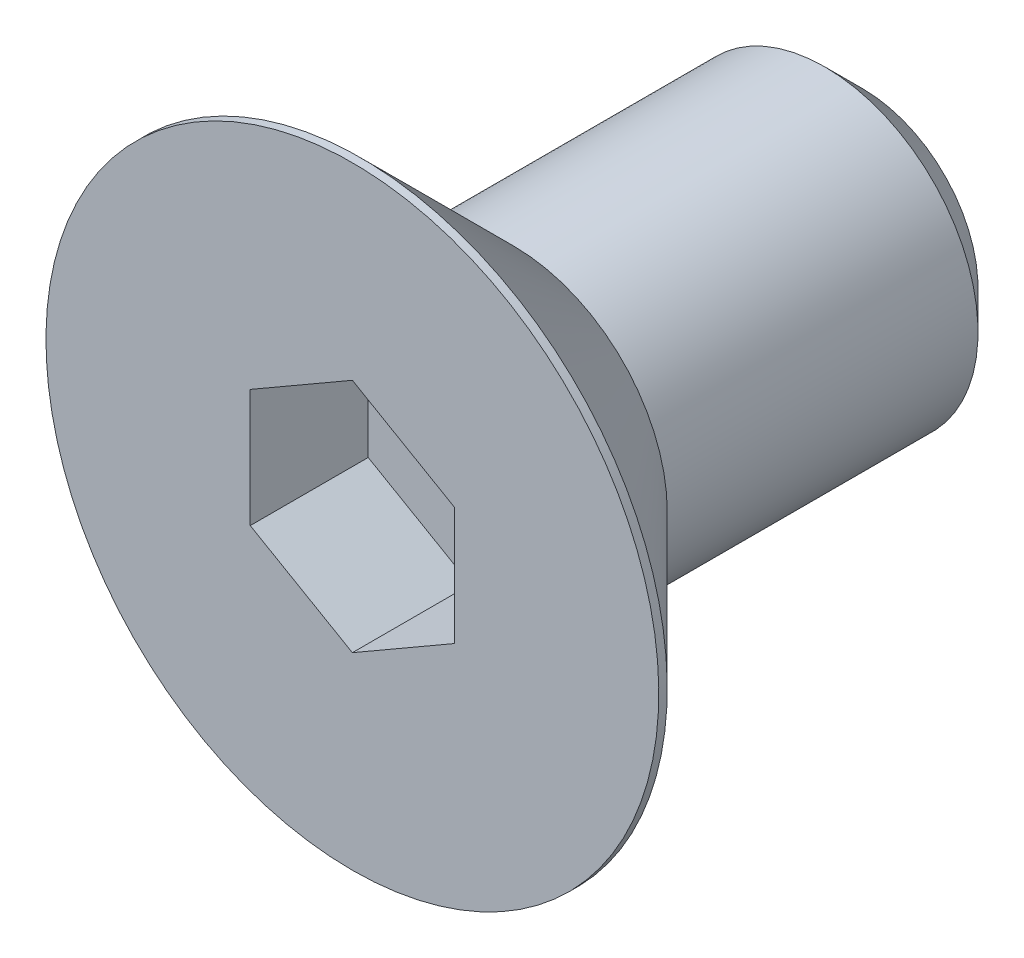
SolidWorks part; units mm, degrees
material "Chrome Stainless Steel"
ref_plane "Front" through (0, 0, 0) normal (0, 0, 1) x (1, 0, 0)
ref_plane "Top" through (0, 0, 0) normal (0, 1, 0) x (1, 0, 0)
ref_plane "Right" through (0, 0, 0) normal (1, 0, 0) x (0, 0, -1)
sketch "Sketch11" plane through (0, 0, 0) normal (1, 0, 0) x (0, 0, -1)
  line L0 (-5, 6) -> (5, 6) construction
  line L5 (-5, 6) -> (-5, -6) construction
  line L6 (5, 3) -> (5, -3) construction
  line L7 (-4.99, 2) -> (-4.99, -2) construction
  line L8 (4.9375, 3.1083) -> (5.9375, 3.1083) construction
  line L9 (5.9375, 3.1083) -> (5.4375, 2.2422) construction
  line L10 (5.4375, 2.2422) -> (4.9375, 3.1083) construction
  line L11 (5.375, 2.3505) -> (5.5, 2.3505) construction
  line L12 (5.4375, 2.3505) -> (5.4375, 2.2422) construction
  line L13 (4.9688, 3.0541) -> (5.9063, 3.0541) construction
  line L14 (5.4375, 3.1083) -> (5.4375, 3) construction
  line L15 (5, 3) -> (5.875, 3) construction
  line L17 (-4.835, 6) -> (1.165, 0) construction
  line L18 (1.165, 0) -> (-4.835, -6) construction
  point P3 (-1.7, 6)
  point P8 (0, 6)
  point P21 (5.4375, 3.0541)
  point P26 (-5, 0)
  point P28 (-4.99, 0)
  point P29 (5, 0)
  dimension "Length" = 10
  dimension "Head Diameter" = 12
  dimension "Thread Major Diameter" = 6
  dimension "Head Height" = 3.3
  dimension "Drive Size" = 4
  dimension "Thread Pitch" = 1
  dimension "D1" = 0.125
  dimension "D2" = 0.01
  dimension "D3" = 0.165
  dimension "Countersink Angle" = 90
sketch "Sketch1" plane through (0, 0, 0) normal (1, 0, 0) x (0, 0, -1)
  line L2 (-1.7, 3) -> (5, 3)
  line L3 (5, 3) -> (5, 0)
  line L4 (-2.69, 3) -> (-2.69, 0)
  line L5 (-1.7, 3) -> (-2.69, 3)
  line L6 (-5, 6) -> (-5, -6) construction
  line L7 (5, 3) -> (5, -3) construction
  line L8 (-2.69, 0) -> (5, 0)
  dimension "D1" = 2.31
revolve "Revolve1" add sketch "Sketch1" angle 360 mid plane about L8
chamfer "Chamfer1" distance 0.75 angle 45 1 edges at (0, -3, -5)
sketch "Sketch7" plane through (0, 0, 0) normal (1, 0, 0) x (0, 0, -1)
  line L2 (-5, 6) -> (-4.835, 6)
  line L5 (-1.7, 2.865) -> (-1.7, 0)
  line L6 (-5, 6) -> (-5, 0)
  line L8 (-5, 6) -> (-5, -6) construction
  line L9 (-5, 0) -> (-1.7, 0)
  line L12 (-4.835, 6) -> (-1.7, 2.865)
  line L13 (-4.835, 6) -> (1.165, 0) construction
revolve "Revolve2" add sketch "Sketch7" angle 360 mid plane about L9 region at (0, 2.3546, 3.5497)
ref_plane "Plane1" through (0, 0, 1.7) normal (0, 0, 1) x (1, 0, 0)
sketch "Sketch5" plane through (0, 0, 5) normal (0, 0, 1) x (1, 0, 0)
  line L1 (2, -1.1547) -> (2, 1.1547)
  line L2 (2, 1.1547) -> (0, 2.3094)
  line L3 (0, 2.3094) -> (-2, 1.1547)
  line L4 (-2, 1.1547) -> (-2, -1.1547)
  line L5 (-2, -1.1547) -> (0, -2.3094)
  line L6 (0, -2.3094) -> (2, -1.1547)
  circle A0 centre (0, 0) radius 2 construction
extrude "Cut-Extrude2" cut sketch "Sketch5" against normal blind 2.31
sketch "Sketch6" plane through (0, 0, 5) normal (0, 0, -1) x (-1, 0, 0)
  circle A0 centre (0, 0) radius 2.3094
extrude "Cut-Extrude3" [suppressed] cut sketch "Sketch6" along normal blind 2.31 draft 45
sketch "Sketch12" [suppressed] plane through (0, 0, -5) normal (0, 0, -1) x (-1, 0, 0)
  circle A0 centre (0, 0) radius 3 construction
  circle A1 centre (0, 0) radius 3
curve "Helix/Spiral1" [suppressed] pitch 1 height 10 turns 10
sketch "Sketch13" [suppressed] plane through (0, 0, 0) normal (1, 0, 0) x (0, 0, -1)
  line L0 (4.9688, 3.0541) -> (5.9063, 3.0541)
  line L1 (5.9063, 3.0541) -> (5.5, 2.3505)
  line L2 (5.5, 2.3505) -> (5.375, 2.3505)
  line L3 (5.375, 2.3505) -> (4.9688, 3.0541)
sweep "Cut-Sweep1" [suppressed] cut profiles "Sketch13" path "Helix/Spiral1"
combine bodies "Combine1" [suppressed] operation type add bodies to combine 113 127
equation "\"D1@Chamfer1\"=\"Thread Pitch@Sketch11\" * .75"
equation "\"D1@Cut-Extrude2\"= \"Head Height@Sketch11\" * .7"
equation "\"D1@Cut-Extrude3\" = \"D1@Cut-Extrude2\""
equation "\"D1@Sketch11\"=\"Thread Pitch@Sketch11\"/8"
equation "\"D3@Sketch11\"=\"Head Height@Sketch11\"*.05"
equation "\"D4@Helix/Spiral1\"=\"Thread Pitch@Sketch11\""
equation "\"D1@Sketch1\"=\"Head Height@Sketch11\"*.7"
equation "\"D3@Helix/Spiral1\"=\"Length@Sketch11\""
